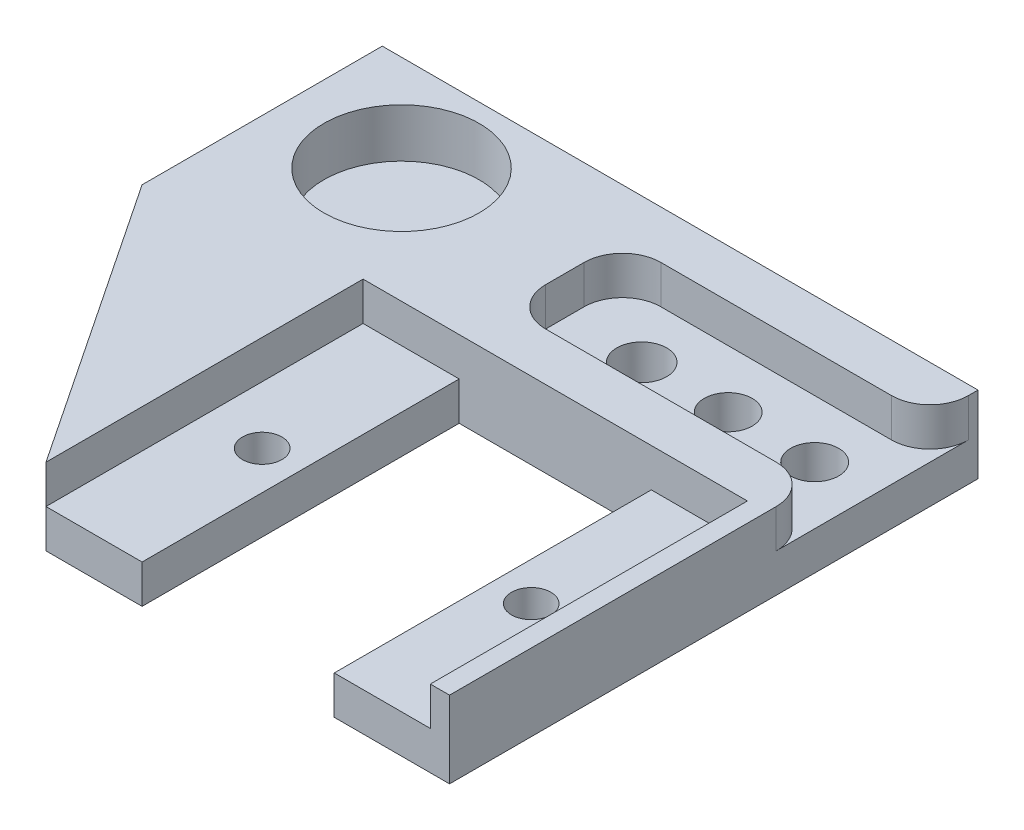
SolidWorks part; units mm, degrees
ref_plane "前视基准面" through (0, 0, 0) normal (0, 0, 1) x (1, 0, 0)
ref_plane "上视基准面" through (0, 0, 0) normal (0, 1, 0) x (1, 0, 0)
ref_plane "右视基准面" through (0, 0, 0) normal (1, 0, 0) x (0, 0, -1)
sketch "草图1" plane through (0, 0, 0) normal (0, 1, 0) x (1, 0, 0)
  line L0 (-160.9101, 0) -> (0, 0) construction
  line L3 (43, 1.5) -> (58.4568, 3.5349)
  line L4 (0, 15) -> (10, 30)
  line L5 (59.9953, -9.8805) -> (31, -30)
  line L6 (10, 30) -> (31, 30)
  line L7 (0, -15) -> (10, -30)
  line L8 (43, -1.5) -> (58.4568, -3.5349)
  line L9 (43, 1.5) -> (40, 1.5)
  line L11 (40, 1.5) -> (40, -1.5)
  line L12 (0, 15) -> (0, -15)
  line L13 (40, -1.5) -> (43, -1.5)
  line L14 (36.676, 0) -> (71.1357, 0) construction
  line L15 (59.9953, 9.8805) -> (31, 30)
  line L16 (10, -30) -> (31, -30)
  arc A3 (58.4568, 3.5349) -> (59.9953, 9.8805) centre (58, 7.005) ccw
  arc A4 (58.4568, -3.5349) -> (59.9953, -9.8805) centre (58, -7.005) cw
  point P33 (40, 0)
  dimension "D2" = 3
  dimension "D3" = 3.5
  dimension "D5" = 7.5
  dimension "D6" = 15
  dimension "D7" = 10
  dimension "D8" = 40
  dimension "D10" = 60
  dimension "D11" = 21
  dimension "D12" = 21
  dimension "D1" = 3
  dimension "D4" = 3
  dimension "D9" = 30
extrude "凸台-拉伸1" add sketch "草图1" along normal blind 2
sketch "草图2" plane through (0, 0, 0) normal (0, -1, 0) x (1, 0, 0)
  line L0 (15, 37.5) -> (15, -37.5)
  line L1 (10, -30) -> (0, -15) construction
  line L12 (10, 30) -> (0, 15)
  line L13 (0, 15) -> (0, -15)
  line L14 (0, -15) -> (10, -30)
  line L15 (31, -30) -> (59.9953, -9.8805)
  line L16 (58.4568, -3.5349) -> (43, -1.5)
  line L17 (43, -1.5) -> (40, -1.5)
  line L18 (40, -1.5) -> (40, 1.5)
  line L19 (40, 1.5) -> (43, 1.5)
  line L20 (43, 1.5) -> (58.4568, 3.5349)
  line L21 (59.9953, 9.8805) -> (31, 30)
  line L22 (10, 30) -> (0, 15)
  line L23 (0, 15) -> (0, -15)
  line L24 (0, -15) -> (10, -30)
  line L25 (31, -30) -> (59.9953, -9.8805)
  line L26 (58.4568, -3.5349) -> (43, -1.5)
  line L27 (43, -1.5) -> (40, -1.5)
  line L28 (40, -1.5) -> (40, 1.5)
  line L29 (40, 1.5) -> (43, 1.5)
  line L30 (43, 1.5) -> (58.4568, 3.5349)
  line L31 (59.9953, 9.8805) -> (31, 30)
  line L34 (31, 30) -> (10, 30)
  line L35 (31, 30) -> (10, 30)
  line L36 (10, -30) -> (31, -30)
  line L37 (10, -30) -> (31, -30)
  arc A6 (59.9953, -9.8805) -> (58.4568, -3.5349) centre (58, -7.005) ccw
  arc A7 (58.4568, 3.5349) -> (59.9953, 9.8805) centre (58, 7.005) ccw
  arc A10 (59.9953, -9.8805) -> (58.4568, -3.5349) centre (58, -7.005) ccw
  arc A11 (58.4568, 3.5349) -> (59.9953, 9.8805) centre (58, 7.005) ccw
  line M17 (10, 30) -> (0, 15)
  line M18 (0, 15) -> (0, -15)
  line M19 (0, -15) -> (10, -30)
  dimension "D2" = 15
  dimension "D1" = 0
extrude "凸台-拉伸2" add sketch "草图2" along normal blind 3 contours L0 M17 M18 M19 region at (8.3333, 0, 0)
sketch "草图3" plane through (0, 0, 0) normal (0, -1, 0) x (1, 0, 0)
  line L3 (31, -30) -> (31, 30)
  line L10 (15, 30) -> (15, -30)
  line L11 (31, -30) -> (59.9953, -9.8805)
  line L12 (58.4568, -3.5349) -> (43, -1.5)
  line L13 (43, -1.5) -> (40, -1.5)
  line L14 (40, -1.5) -> (40, 1.5)
  line L15 (40, 1.5) -> (43, 1.5)
  line L16 (43, 1.5) -> (58.4568, 3.5349)
  line L17 (59.9953, 9.8805) -> (31, 30)
  line L18 (15, 30) -> (15, -30)
  line L28 (31, 30) -> (15, 30)
  line L29 (31, 30) -> (15, 30)
  line L30 (15, -30) -> (31, -30)
  line L31 (15, -30) -> (31, -30)
  arc A7 (59.9953, -9.8805) -> (58.4568, -3.5349) centre (58, -7.005) ccw
  arc A8 (58.4568, 3.5349) -> (59.9953, 9.8805) centre (58, 7.005) ccw
  dimension "D2" = 0
extrude "凸台-拉伸3" add sketch "草图3" along normal blind 3
sketch "草图4" plane through (0, 2, 0) normal (0, 1, 0) x (1, 0, 0)
  line L0 (0, 0) -> (40, 0) construction
  line L1 (40, -1.5) -> (40, 1.5) construction
  line L2 (31, 30) -> (10, 30) construction
  line L7 (15, -30.0542) -> (25, -30)
  line L8 (10, -30) -> (31, -30) construction
  line L9 (25, -30) -> (25, -13.5)
  line L10 (25, -13.5) -> (15, -13.5)
  line L11 (15, -13.5) -> (15, -30.0542)
  line L12 (31, 30) -> (10, 30) construction
  line L13 (25, 13.5) -> (15, 13.5)
  line L14 (25, 30) -> (25, 13.5)
  line L15 (15, 30.0542) -> (25, 30)
  line L16 (15, 13.5) -> (15, 30.0542)
  dimension "D1" = 10
  dimension "D2" = 16.5
  dimension "D3" = 5
sketch "草图5" plane through (0, -3, 0) normal (0, -1, 0) x (1, 0, 0)
  line L6 (10, -30) -> (31, -30)
  line L7 (31, -30) -> (31, 30)
  line L8 (31, 30) -> (10, 30)
  line L9 (10, 30) -> (0, 15)
  line L10 (0, 15) -> (0, -15)
  line L11 (0, -15) -> (10, -30)
  line L12 (10, -30) -> (31, -30)
  line L13 (31, -30) -> (31, 30)
  line L14 (31, 30) -> (10, 30)
  line L15 (10, 30) -> (0, 15)
  line L16 (0, 15) -> (0, -15)
  line L17 (0, -15) -> (10, -30)
  dimension "D1" = 0
extrude "切除-拉伸1" cut sketch "草图5" against normal blind 1
extrude "切除-拉伸2" cut sketch "草图4" against normal through all
sketch "草图6" plane through (0, 2, 0) normal (0, 1, 0) x (1, 0, 0)
  line L1 (10, 30) -> (30, 30)
  line L2 (10, 30) -> (10, 13.5)
  line L3 (10, 13.5) -> (30, 13.5)
  line L4 (30, 30) -> (30, 13.5)
  line L5 (10, -30) -> (30, -30)
  line L6 (10, -30) -> (10, -13.5)
  line L7 (10, -13.5) -> (30, -13.5)
  line L8 (30, -30) -> (30, -13.5)
  dimension "D1" = 16.5
  dimension "D2" = 20
  dimension "D3" = 20
  dimension "D4" = 16.5
extrude "切除-拉伸4" cut sketch "草图6" against normal blind 2
sketch "草图10" plane through (0, 2, 0) normal (0, 1, 0) x (1, 0, 0)
  line L0 (40, -1.5) -> (-11.1008, -1.5)
  line L1 (-11.1008, -1.5) -> (-3.8541, 32.231)
  line L2 (-3.8541, 32.231) -> (54.2038, 29.6188)
  line L3 (54.2038, 29.6188) -> (85.4645, 13.0419)
  line L4 (85.4645, 13.0419) -> (77.3764, 2.6543)
  line L5 (77.3764, 2.6543) -> (40, -1.5)
extrude "切除-拉伸6" cut sketch "草图10" against normal through all both and the other way through all
sketch "草图11" plane through (0, 2, 0) normal (0, 1, 0) x (1, 0, 0)
  line L7 (31, -34.8686) -> (62.2757, -13.1669)
  line L9 (43, -1.5) -> (0, -1.5)
  line L10 (0, -1.5) -> (0, -15)
  line L11 (0, -15) -> (10, -30)
  line L12 (10, -30) -> (10, -13.5)
  line L13 (10, -13.5) -> (30, -13.5)
  line L14 (30, -13.5) -> (30, -30)
  line L15 (30, -30) -> (31, -30)
  line L16 (31, -30) -> (59.9953, -9.8805)
  line L17 (58.4568, -3.5349) -> (43, -1.5)
  line L25 (31, -30) -> (59.9953, -9.8805)
  line L26 (65.0333, -4.4007) -> (58.4568, -3.5349)
  line L27 (14, -17.5) -> (26, -17.5) construction
  line L28 (-4, -16.2111) -> (14, -43.2111) construction
  line L29 (14, -43.2111) -> (14, -17.5) construction
  line L30 (-4, 2.5) -> (-4, -16.2111) construction
  line L31 (43.2622, 2.5) -> (-4, 2.5) construction
  line L32 (58.9789, 0.4308) -> (43.2622, 2.5) construction
  line L33 (58.4568, -3.5349) -> (43, -1.5) construction
  line L34 (31, -30) -> (31, -34)
  line L35 (26, -34) -> (32.2518, -34) construction
  line L36 (10, -13.5) -> (30, -13.5) construction
  line L37 (10, -30) -> (10, -13.5) construction
  line L38 (0, -15) -> (10, -30) construction
  line L39 (0, -1.5) -> (0, -15) construction
  line L40 (43, -1.5) -> (0, -1.5) construction
  line L41 (26, -17.5) -> (26, -34) construction
  line L42 (30, -13.5) -> (30, -30) construction
  line L43 (30, -30) -> (31, -30) construction
  line L44 (31, -34) -> (31, -34.8686)
  line L45 (32.2518, -34) -> (62.2757, -13.1669) construction
  arc A0 (62.2757, -13.1669) -> (65.0333, -4.4007) centre (58, -7.005) ccw
  arc A1 (59.9953, -9.8805) -> (58.4568, -3.5349) centre (58, -7.005) ccw
  arc A2 (59.9953, -9.8805) -> (58.4568, -3.5349) centre (58, -7.005) ccw
  arc A3 (62.2757, -13.1669) -> (58.9789, 0.4308) centre (58, -7.005) ccw construction
  dimension "D1" = 0
  dimension "D2" = 4
extrude "凸台-拉伸4" add sketch "草图11" against normal blind 1
sketch "草图12" plane through (0, 2, 0) normal (0, 1, 0) x (1, 0, 0)
  line L0 (0, -1.5) -> (0, -15) construction
  line L1 (43, -1.5) -> (0, -1.5) construction
  circle A0 centre (58, -7.005) radius 1
  circle A1 centre (43, -6) radius 1
  circle A2 centre (6, -7.25) radius 4
  dimension "D1" = 2
  dimension "D2" = 2
  dimension "D4" = 8
  dimension "D6" = 5.75
  dimension "D3" = 4.5
  dimension "D5" = 6
extrude "切除-拉伸7" cut sketch "草图12" against normal blind 2.54
sketch "草图13" plane through (0, 0, 0) normal (0, 1, 0) x (1, 0, 0)
  line L0 (25, -30) -> (25, -13.5) construction
  line L1 (15, -13.5) -> (15, -30) construction
  line L2 (10, -30) -> (15, -30) construction
  line L3 (25, -30) -> (30, -30) construction
  circle A0 centre (13, -21.75) radius 1.25
  circle A1 centre (27, -21.75) radius 1.25
  dimension "D1" = 2.5
  dimension "D2" = 2.5
  dimension "D3" = 2
  dimension "D4" = 2
  dimension "D5" = 8.25
  dimension "D6" = 8.25
extrude "切除-拉伸8" cut sketch "草图13" against normal blind 10
sketch "草图15" plane through (0, 1, 0) normal (0, -1, 0) x (1, 0, 0)
  line L1 (31, 30) -> (31, 34.8686) construction
  line L2 (30.1449, 33.6363) -> (61.4205, 11.9345)
  line L3 (30.1449, 33.6363) -> (61.4205, 11.9345) construction
  circle A0 centre (36, 29.5735) radius 1
  circle A1 centre (56, 15.6957) radius 1
  dimension "D3" = 20
  dimension "D4" = 2
  dimension "D5" = 2
  dimension "D2" = 5
  dimension "D1" = 1.5
extrude "切除-拉伸10" cut sketch "草图15" against normal blind 10
sketch "草图16" plane through (0, 0, 0) normal (0, -1, 0) x (1, 0, 0)
  circle A2 centre (58, 7.005) radius 1.02
  circle A3 centre (58, 7.005) radius 1.02
  circle A5 centre (43, 6) radius 1.02
  circle A6 centre (43, 6) radius 1.02
  dimension "D1" = 0.02
  dimension "D2" = 0.02
extrude "切除-拉伸11" cut sketch "草图16" against normal up to surface (2 mm away) up to face at (36, 2, 28.5735)
sketch "草图18" plane through (0, -2, 0) normal (0, -1, 0) x (1, 0, 0)
  point P0 (13, 21.75)
  point P1 (27, 21.75)
  point P3 (36, 29.5735)
  point P5 (56, 15.6957)
sketch "草图19" plane through (0, -2, 0) normal (0, -1, 0) x (1, 0, 0)
  circle A0 centre (13, 21.75) radius 1.8084
  circle A1 centre (27, 21.75) radius 1.7981
  circle A2 centre (36, 29.5735) radius 1.2311
  circle A3 centre (56, 15.6957) radius 1.3586
  circle M4 centre (27, 21.75) radius 1.25
extrude "凸台-拉伸5" add sketch "草图19" against normal up to surface (2 mm away) contours A1 M4 | A0 | A1 region at (25.2528, -2, 21.75) up to face at (13, 0, 23)
extrude "凸台-拉伸6" add sketch "草图19<3>" against normal up to surface (4 mm away) from surface contours A2 | A3 up to face at (58, 2, 5.985) starting at face at (36, 1, 28.5735)
sketch "草图19<3>" plane through (0, -2, 0) normal (0, -1, 0) x (1, 0, 0) same geometry as "草图19"
hole_wizard "M2.5 螺纹孔1" positions "草图20" profile "草图21" tap size "M2.5" standard "GB" end condition through all
sketch "草图20" plane through (0, -2, 0) normal (0, -1, 0) x (-1, 0, 0)
  point P0 (-27, -21.75)
  point P3 (-13, -21.75)
sketch "草图21" plane through (27, -2, 21.75) normal (1, 0, 0) x (0, 0, -1)
  line L0 (0, 0) -> (0, 4)
  line L1 (0, 4) -> (1.025, 4)
  line L2 (1.025, 4) -> (1.025, 0)
  line L5 (1.025, 0) -> (0, 0)
  line L11 (0, -6.35) -> (0, 107.95) construction
  dimension "通孔螺纹孔钻头直径" = 2.05
  dimension "通孔螺纹孔钻头深度" = 4
hole_wizard "M2 螺纹孔1" positions "草图22" profile "草图23" tap size "M2" standard "GB" end condition through all
sketch "草图22" plane through (0, 1, 0) normal (0, -1, 0) x (-1, 0, 0)
  point P0 (-56, -15.6957)
  point P3 (-36, -29.5735)
sketch "草图23" plane through (56, 1, 15.6957) normal (1, 0, 0) x (0, 0, -1)
  line L0 (0, 0) -> (0, 1)
  line L1 (0, 1) -> (0.8, 1)
  line L2 (0.8, 1) -> (0.8, 0)
  line L5 (0.8, 0) -> (0, 0)
  line L11 (0, -6.35) -> (0, 107.95) construction
  dimension "通孔螺纹孔钻头直径" = 1.6
  dimension "通孔螺纹孔钻头深度" = 1
sketch "草图25" plane through (0, 2, 0) normal (0, 1, 0) x (1, 0, 0)
  circle A0 centre (6, -7.25) radius 4.02
  dimension "D1" = 8.04
extrude "切除-拉伸12" cut sketch "草图25" against normal blind 2.54
sketch "草图30" plane through (0, -2, 0) normal (0, -1, 0) x (1, 0, 0)
  line L1 (0, 1.5) -> (55.3066, 1.5)
  line L2 (0, 1.5) -> (0, 2)
  line L3 (0, 2) -> (55.3066, 2)
  line L4 (55.3066, 1.5) -> (55.3066, 2)
  dimension "D1" = 0.5
extrude "切除-拉伸17" cut sketch "草图30" against normal through all
sketch "草图31" plane through (0, 0, 0) normal (0, -1, 0) x (1, 0, 0)
  line L1 (31, 2) -> (78.75, 2)
  line L2 (31, 2) -> (31, 38.8909)
  line L3 (31, 38.8909) -> (78.75, 38.8909)
  line L4 (78.75, 2) -> (78.75, 38.8909)
extrude "切除-拉伸18" cut sketch "草图31" against normal through all
sketch "草图32" plane through (0, 2, 0) normal (0, 1, 0) x (1, 0, 0)
  line L0 (31, -30) -> (31, -2) construction
  line L1 (31, -11) -> (15, -11)
  line L2 (31, -11) -> (31, -5)
  line L3 (31, -5) -> (15, -5)
  line L4 (15, -11) -> (15, -5)
  line L5 (30, -13.5) -> (25, -13.5) construction
  dimension "D1" = 2.5
  dimension "D2" = 6
  dimension "D3" = 16
extrude "切除-拉伸19" cut sketch "草图32" against normal blind 2
fillet "圆角2" radius 2 4 edges at (15, 1, 11) (15, 1, 5) (31, 1, 11) (31, 1, 5)
sketch "草图33" plane through (0, 0, 0) normal (0, 1, 0) x (1, 0, 0)
  line L0 (15, -7) -> (15, -9) construction
  line L1 (31, -13) -> (31, -3) construction
  circle A0 centre (19, -8) radius 1.25
  circle A1 centre (23.5, -8) radius 1.25
  circle A2 centre (28, -8) radius 1.25
  point P9 (15, -8)
  dimension "D1" = 9
  dimension "D2" = 4.5
  dimension "D3" = 3
  dimension "D4" = 2.5
extrude "切除-拉伸20" cut sketch "草图33" against normal blind 2
sketch "草图34" plane through (0, 2, 0) normal (0, 1, 0) x (1, 0, 0)
  point P0 (6, -7.25)
sketch "草图35" plane through (0, 2, 0) normal (0, 1, 0) x (1, 0, 0)
  circle A1 centre (6, -7.25) radius 4.02
  circle A2 centre (6, -7.25) radius 4.02
  dimension "D1" = 0
extrude "凸台-拉伸7" add sketch "草图35" against normal up to surface (4 mm away) up to face at (19, -2, 9.25)
sketch "草图36" plane through (0, 2, 0) normal (0, 1, 0) x (1, 0, 0)
  circle A0 centre (6, -7.5) radius 4.04
  dimension "D1" = 8.08
  dimension "D2" = 0.25
extrude "切除-拉伸21" cut sketch "草图36" against normal blind 2.54
sketch "草图37" plane through (0, 2, 0) normal (0, 1, 0) x (1, 0, 0)
  line L1 (0, -2) -> (31, -2)
  line L2 (0, -2) -> (0, -2.5)
  line L3 (0, -2.5) -> (31, -2.5)
  line L4 (31, -2) -> (31, -2.5)
  dimension "D1" = 0.5
extrude "切除-拉伸22" cut sketch "草图37" against normal blind 10
sketch "草图38" plane through (0, -2, 0) normal (0, -1, 0) x (1, 0, 0)
  circle A0 centre (19, 8) radius 1.3
  dimension "D1" = 2.6
extrude "切除-拉伸23" cut sketch "草图38" against normal through all
